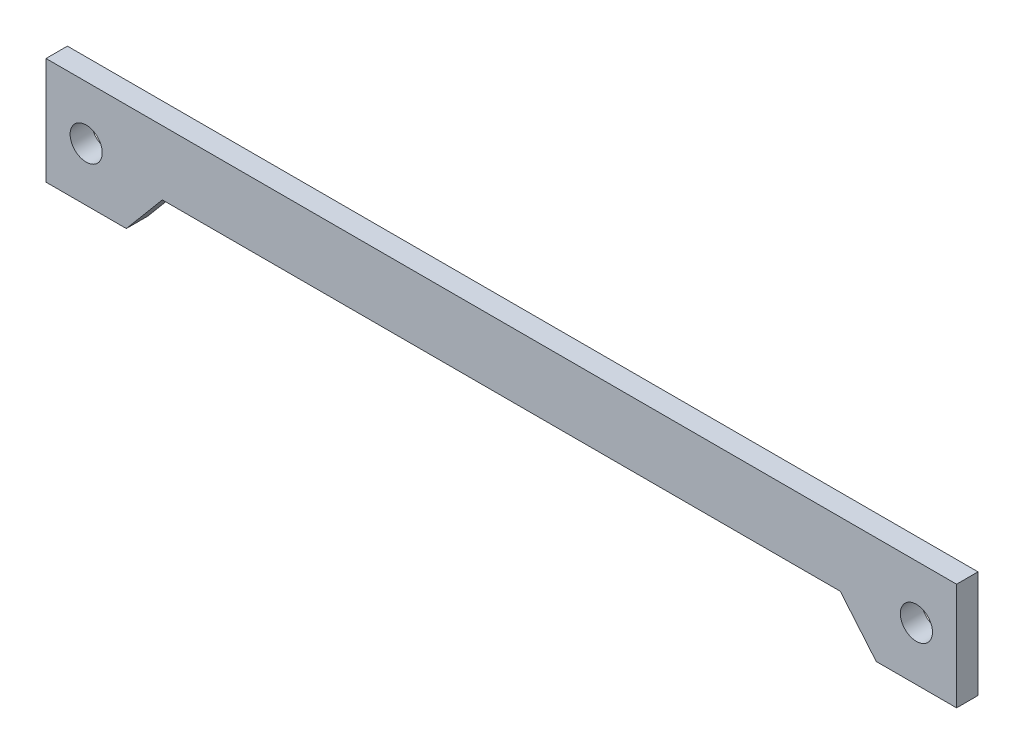
SolidWorks part; units mm, degrees
material "Pappelsperrholz"
ref_plane "Ebene vorne" through (0, 0, 0) normal (0, 0, 1) x (1, 0, 0)
ref_plane "Ebene oben" through (0, 0, 0) normal (0, 1, 0) x (1, 0, 0)
ref_plane "Ebene rechts" through (0, 0, 0) normal (1, 0, 0) x (0, 0, -1)
sketch "Skizze1" plane through (0, 0, 0) normal (0, 0, 1) x (1, 0, 0)
  line L0 (0, 0) -> (0, -22.0536) construction
  line L1 (85, 0) -> (-85, 0)
  line L2 (-85, 0) -> (-85, -20)
  line L3 (-85, -20) -> (-70, -20)
  line L4 (-70, -20) -> (-63.2872, -12)
  line L5 (-63.2872, -12) -> (63.2872, -12)
  line L6 (70, -20) -> (63.2872, -12)
  line L7 (85, -20) -> (70, -20)
  line L8 (85, 0) -> (85, -20)
  point P9 (0, -12)
  dimension "D1" = 170
  dimension "D2" = 20
  dimension "D3" = 12
  dimension "D4" = 15
  dimension "D5" = 130
extrude "Grundplatte" add sketch "Skizze1" along normal blind 4
sketch "Skizze2" plane through (0, 0, 4) normal (0, 0, 1) x (1, 0, 0)
  line L0 (0, 0) -> (0, -12) construction
  line L1 (-63.2872, -12) -> (63.2872, -12) construction
  line L2 (85, 0) -> (-85, 0) construction
  circle A0 centre (-77.5, -10) radius 3
  circle A1 centre (77.5, -10) radius 3
  dimension "D1" = 6
  dimension "D3" = 155
  dimension "D2" = 10
extrude "Schnitt-Linear austragen1" cut sketch "Skizze2" against normal through all
